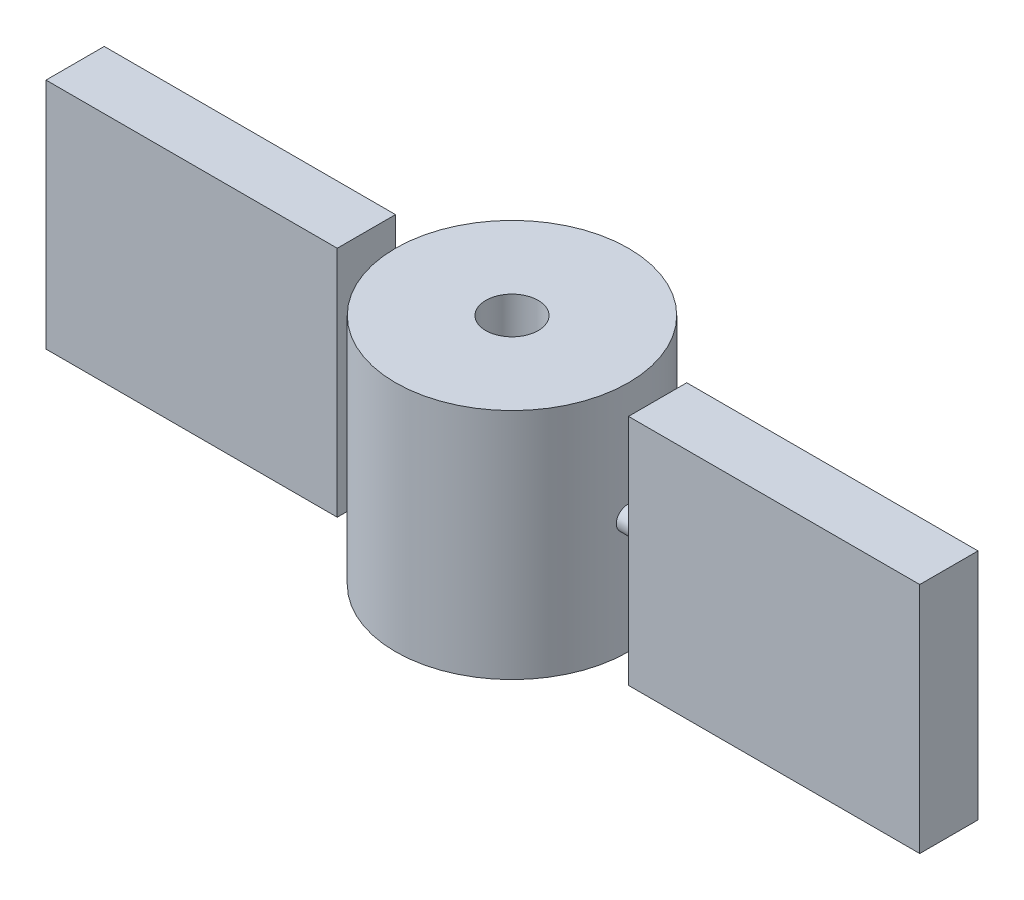
SolidWorks part; units mm, degrees
ref_plane "Front Plane" through (0, 0, 0) normal (0, 0, 1) x (1, 0, 0)
ref_plane "Top Plane" through (0, 0, 0) normal (0, 1, 0) x (1, 0, 0)
ref_plane "Right Plane" through (0, 0, 0) normal (1, 0, 0) x (0, 0, -1)
sketch "Sketch1" plane through (0, 0, 0) normal (0, 1, 0) x (1, 0, 0)
  circle A0 centre (0, 0) radius 20
  dimension "D1" = 40
extrude "Boss-Extrude1" add sketch "Sketch1" along normal blind 40
sketch "Sketch2" plane through (0, 0, 0) normal (0, 0, 1) x (1, 0, 0)
  line L0 (0, 0) -> (0, 40) construction
  line L1 (20, 40) -> (-20, 40) construction
  line L2 (0, 20) -> (-20, 20)
  line L3 (-20, 40) -> (-20, 0) construction
  line L4 (0, 20) -> (20, 20)
  line L5 (20, 0) -> (20, 40) construction
  line L6 (-20, 20) -> (-50, 20)
  line L7 (20, 20) -> (50, 20)
  line L9 (25, 40) -> (75, 40)
  line L10 (25, 40) -> (25, 0)
  line L11 (25, 0) -> (75, 0)
  line L12 (75, 40) -> (75, 0)
  line L13 (25, 40) -> (75, 0) construction
  line L14 (25, 0) -> (75, 40) construction
  line L15 (-75, 40) -> (-25, 40)
  line L16 (-75, 40) -> (-75, 0)
  line L17 (-75, 0) -> (-25, 0)
  line L18 (-25, 40) -> (-25, 0)
  line L19 (-75, 40) -> (-25, 0) construction
  line L20 (-75, 0) -> (-25, 40) construction
  dimension "D1" = 50
  dimension "D2" = 40
  dimension "D3" = 50
  dimension "D4" = 40
  dimension "D5" = 50
  dimension "D6" = 50
extrude "Boss-Extrude2" add sketch "Sketch2" along normal mid plane 10 separate body contours L18 L15 L16 L17 | L12 L9 L10 L11 region at (-25.6403, 10, 0) region at (25.6403, 30, 0)
sketch "Sketch7" plane through (0, 0, 0) normal (1, 0, 0) x (0, 0, -1)
  line L0 (0, 40) -> (0, 0) construction
  circle A0 centre (0, 20) radius 2
  dimension "D1" = 4
extrude "Boss-Extrude3" add sketch "Sketch7" along normal mid plane 100
sketch "Sketch8" plane through (0, 0, 0) normal (0, 0, 1) x (1, 0, 0)
  line L0 (-20, 40) -> (20, 40)
  line L1 (20, 40) -> (-20, 40) construction
  line L2 (20, 22) -> (20, 40) construction
  arc A0 (20, 40) -> (-20, 40) centre (0, 40) ccw
sketch "Sketch9" plane through (0, 40, 0) normal (0, 1, 0) x (1, 0, 0)
  circle A0 centre (0, 0) radius 4.5
  circle A1 centre (0, 0) radius 2.15
  dimension "D1" = 9
  dimension "D2" = 4.3
extrude "Cut-Extrude1" cut sketch "Sketch9" against normal blind 30 contours A0 A1 | A1 region at (-4.3727, 40, 0) region at (0, 40, 0)
extrude "Cut-Extrude2" cut sketch "Sketch9<3>" against normal through all contours A1 region at (0, 40, 0)
sketch "Sketch9<3>" plane through (0, 40, 0) normal (0, 1, 0) x (1, 0, 0) same geometry as "Sketch9"
